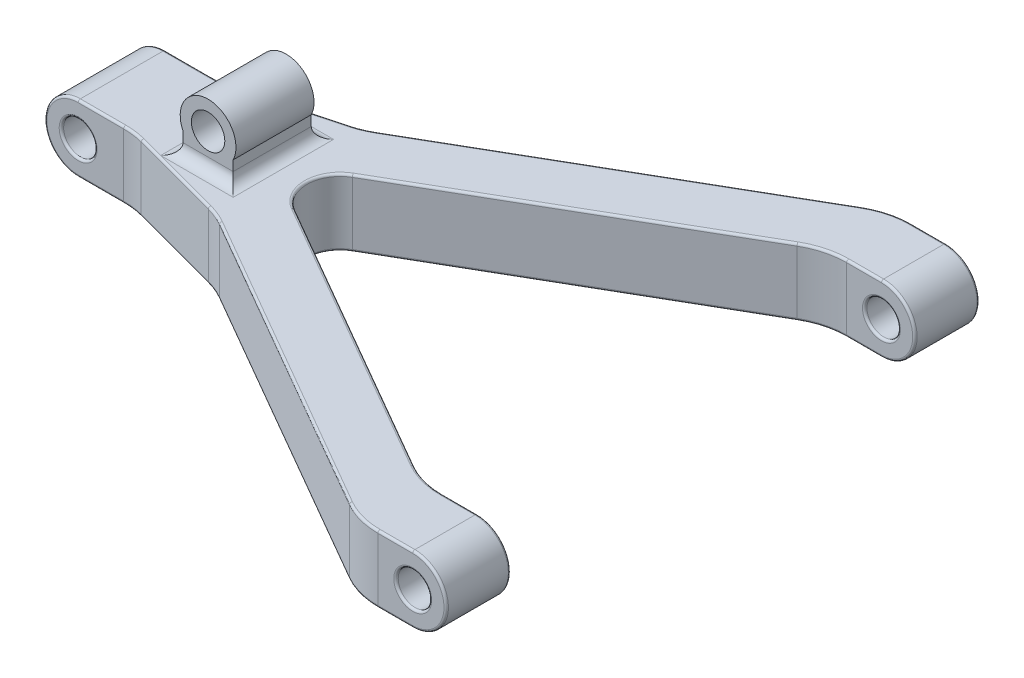
SolidWorks part; units mm, degrees
ref_plane "Front Plane" through (0, 0, 0) normal (0, 0, 1) x (1, 0, 0)
ref_plane "Top Plane" through (0, 0, 0) normal (0, 1, 0) x (1, 0, 0)
ref_plane "Right Plane" through (0, 0, 0) normal (1, 0, 0) x (0, 0, -1)
sketch "Sketch1" plane through (0, 0, 0) normal (0, 1, 0) x (1, 0, 0)
  line L0 (0, 0) -> (336.4065, 0) construction
  line L1 (-193.529, -39) -> (-193.529, 39)
  line L2 (-193.529, 39) -> (-143.529, 39)
  line L3 (-143.529, 39) -> (-43.529, 65.7949)
  line L4 (-43.529, 65.7949) -> (256.471, 239)
  line L5 (256.471, 239) -> (306.471, 239)
  line L6 (256.471, -239) -> (306.471, -239)
  line L7 (-43.529, -65.7949) -> (256.471, -239)
  line L8 (-143.529, -39) -> (-43.529, -65.7949)
  line L9 (-193.529, -39) -> (-143.529, -39)
  line L10 (306.471, 239) -> (306.471, 181.26)
  line L11 (306.471, 181.26) -> (256.4624, 181.26)
  line L12 (256.4624, 181.26) -> (-12.4892, 25.9808)
  line L13 (-12.4892, -25.9808) -> (256.4624, -181.26)
  line L14 (256.4624, -181.26) -> (306.471, -181.26)
  line L15 (306.471, -181.26) -> (306.471, -239)
  arc A0 (-12.4892, 25.9808) -> (-12.4892, -25.9808) centre (2.5108, 0) ccw
  point P14 (-193.529, 0)
  dimension "D12" = 30
  dimension "D1" = 39
  dimension "D2" = 100
  dimension "D3" = 300
  dimension "D4" = 50
  dimension "D5" = 500
  dimension "D6" = 165
  dimension "D7" = 165
  dimension "D8" = 50
  dimension "D9" = 57.74
  dimension "D10" = 57.74
  dimension "D11" = 362.52
extrude "Boss-Extrude1" add sketch "Sketch1" along normal blind 60
sketch "Sketch2" plane through (0, 0, 39) normal (0, 0, 1) x (1, 0, 0)
  line L0 (-193.529, 60) -> (-193.529, 0) construction
  circle A0 centre (-193.529, 30) radius 30
extrude "Boss-Extrude2" add sketch "Sketch2" against normal up to surface (78 mm away) up to face at (-168.529, 30, -39)
sketch "Sketch3" plane through (0, 0, 39) normal (0, 0, 1) x (1, 0, 0)
  line L3 (-143.529, 60) -> (-193.529, 60)
  line L4 (-193.529, 0) -> (-143.529, 0)
  line L5 (-143.529, 0) -> (-143.529, 60)
  line L6 (-143.529, 60) -> (-193.529, 60)
  line L7 (-193.529, 0) -> (-143.529, 0)
  line L8 (-143.529, 0) -> (-143.529, 60)
  circle A0 centre (-193.529, 30) radius 15
  arc A1 (-193.529, 60) -> (-193.529, 0) centre (-193.529, 30) ccw
  arc A2 (-193.529, 60) -> (-193.529, 0) centre (-193.529, 30) ccw
  dimension "D2" = 30
  dimension "D1" = 0
extrude "Cut-Extrude1" cut sketch "Sketch3" against normal up to surface (78 mm away) contours A0 up to face at (-176.029, 30, -39)
sketch "Sketch4" plane through (0, 0, -239) normal (0, 0, -1) x (-1, 0, 0)
  line L0 (-306.471, 60) -> (-306.471, 0) construction
  circle A0 centre (-306.471, 30) radius 30
extrude "Boss-Extrude3" add sketch "Sketch4" against normal up to surface (57.74 mm away) up to face at (281.4667, 30, -181.26)
sketch "Sketch5" plane through (0, 0, 239) normal (0, 0, 1) x (1, 0, 0)
  line L0 (306.471, 60) -> (306.471, 0) construction
  circle A0 centre (306.471, 30) radius 30
extrude "Boss-Extrude4" add sketch "Sketch5" against normal up to surface (57.74 mm away) up to face at (281.4667, 30, 181.26)
sketch "Sketch7" plane through (0, 0, -239) normal (0, 0, -1) x (-1, 0, 0)
  line L3 (-256.471, 60) -> (-306.471, 60)
  line L4 (-306.471, 0) -> (-256.471, 0)
  line L5 (-256.471, 0) -> (-256.471, 60)
  line L6 (-256.471, 60) -> (-306.471, 60)
  line L7 (-306.471, 0) -> (-256.471, 0)
  line L8 (-256.471, 0) -> (-256.471, 60)
  circle A0 centre (-306.471, 30) radius 15
  arc A1 (-306.471, 60) -> (-306.471, 0) centre (-306.471, 30) ccw
  arc A2 (-306.471, 60) -> (-306.471, 0) centre (-306.471, 30) ccw
  dimension "D2" = 30
  dimension "D1" = 0
extrude "Cut-Extrude2" cut sketch "Sketch7" against normal through all both and the other way through all contours A0
fillet "Fillet1" radius 70 8 edges at (-143.529, 30, -39) (-143.529, 30, 39) (256.471, 30, 239) (-43.529, 30, 65.7949) (256.4624, 30, 181.26) (256.4624, 30, -181.26) (256.471, 30, -239) (-43.529, 30, -65.7949)
fillet "Fillet2" radius 2 54 edges at (336.471, 30, 181.26) (290.8449, 60, 181.26) (257.1015, 60, 178.8748) (113.8648, 60, 98.9313) (-27.4892, 60, 0) (113.8648, 60, -98.9313) (257.1015, 60, -178.8748) (290.8449, 60, -181.26) (336.471, 30, -181.26) (336.471, 30, -239) (290.8492, 60, -239) (257.1101, 60, -236.6148) (102.3397, 60, -150.0123) (-43.7602, 60, -66.353) (-93.529, 60, -52.3975) (-143.6079, 60, -39.5989) (-173.1369, 60, -39) (-223.529, 30, -39) (-223.529, 30, 39) (-173.1369, 60, 39) (-143.6079, 60, 39.5989) (-93.529, 60, 52.3975) (-43.7602, 60, 66.353) (102.3397, 60, 150.0123) (257.1101, 60, 236.6148) (290.8492, 60, 239) (336.471, 30, 239) (321.471, 30, 181.26) (291.471, 30, 239) (291.471, 30, -181.26) (321.471, 30, -239) (-178.529, 30, 39) (-178.529, 30, -39) (290.8449, 0, 181.26) (257.1015, 0, 178.8748) (113.8648, 0, 98.9313) (-27.4892, 0, 0) (113.8648, 0, -98.9313) (257.1015, 0, -178.8748) (290.8449, 0, -181.26) (290.8492, 0, -239) (257.1101, 0, -236.6148) (102.3397, 0, -150.0123) (-43.7602, 0, -66.353) (-93.529, 0, -52.3975) (-143.6079, 0, -39.5989) (-173.1369, 0, -39) (-173.1369, 0, 39) (-143.6079, 0, 39.5989) (-93.529, 0, 52.3975) (-43.7602, 0, 66.353) (102.3397, 0, 150.0123) (257.1101, 0, 236.6148) (290.8492, 0, 239)
sketch "Sketch8" plane through (0, 60, 0) normal (0, 1, 0) x (1, 0, 0)
  line L0 (-193.529, 37) -> (-193.529, -37) construction
  line L1 (-103.529, 35) -> (-58.529, 35)
  line L2 (-103.529, 35) -> (-103.529, -35)
  line L3 (-103.529, -35) -> (-58.529, -35)
  line L4 (-58.529, 35) -> (-58.529, -35)
  line L5 (-103.529, 35) -> (-58.529, -35) construction
  line L6 (-103.529, -35) -> (-58.529, 35) construction
  point P0 (-81.029, 0)
  point P5 (0, 0)
  dimension "D1" = 45
  dimension "D2" = 70
  dimension "D3" = 90
extrude "Boss-Extrude5" add sketch "Sketch8" along normal blind 30
sketch "Sketch11" plane through (0, 0, 35) normal (0, 0, 1) x (1, 0, 0)
  line L0 (-103.529, 90) -> (-58.529, 90) construction
  circle A0 centre (-81.029, 90) radius 25
  dimension "D1" = 50
extrude "Boss-Extrude6" add sketch "Sketch11" against normal up to surface (70 mm away) up to face at (-81.029, 75, -35)
sketch "Sketch12" plane through (0, 0, 35) normal (0, 0, 1) x (1, 0, 0)
  line L3 (-58.529, 60) -> (-58.529, 79.1028)
  line L4 (-103.529, 79.1028) -> (-103.529, 60)
  line L5 (-103.529, 60) -> (-58.529, 60)
  line L6 (-58.529, 60) -> (-58.529, 79.1028)
  line L7 (-103.529, 79.1028) -> (-103.529, 60)
  line L8 (-103.529, 60) -> (-58.529, 60)
  circle A0 centre (-81.029, 90) radius 15
  arc A1 (-58.529, 79.1028) -> (-103.529, 79.1028) centre (-81.029, 90) ccw
  arc A2 (-58.529, 79.1028) -> (-103.529, 79.1028) centre (-81.029, 90) ccw
  dimension "D2" = 30
  dimension "D1" = 0
extrude "Cut-Extrude3" cut sketch "Sketch12" against normal through all contours A0
fillet "Fillet3" radius 10 4 edges at (-81.029, 60, 35) (-58.529, 60, 0) (-81.029, 60, -35) (-103.529, 60, 0)
